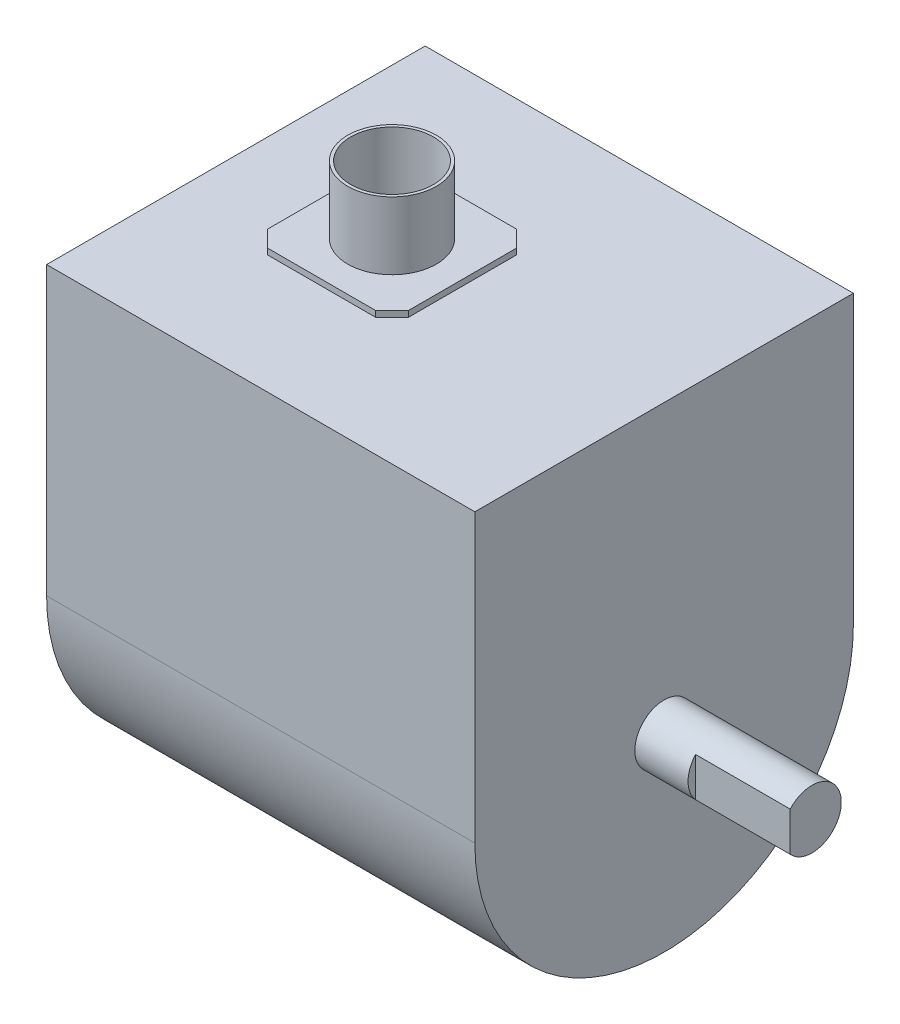
SolidWorks part; units mm, degrees
ref_plane "Front Plane" through (0, 0, 0) normal (0, 0, 1) x (1, 0, 0)
ref_plane "Top Plane" through (0, 0, 0) normal (0, 1, 0) x (1, 0, 0)
ref_plane "Right Plane" through (0, 0, 0) normal (1, 0, 0) x (0, 0, -1)
sketch "Sketch2" plane through (0, 0, 0) normal (1, 0, 0) x (0, 0, -1)
  line L1 (32, 24.25) -> (-32, 24.25)
  line L2 (32, 24.25) -> (32, -24.25)
  line L3 (32, -24.25) -> (-32, -24.25)
  line L4 (-32, 24.25) -> (-32, -24.25)
  line L5 (32, 24.25) -> (-32, -24.25) construction
  line L6 (32, -24.25) -> (-32, 24.25) construction
  arc A0 (32, -24.25) -> (-32, -24.25) centre (0, -24.25) cw
  circle A1 centre (0, -24.25) radius 4.953
  point P0 (0, 0)
  dimension "D3" = 9.906
  dimension "D1" = 48.5
  dimension "D2" = 64
extrude "Boss-Extrude1" add sketch "Sketch2" against normal blind 72.4 contours A1 L3 L2 L1 L4 | A1 L3 A0 | L3 A1 | L3 A1 region at (0, 0.2784, 0) region at (0, -38.113, 0) region at (0, -26.3521, 0) region at (0, -22.1479, 0)
sketch "Sketch3" plane through (0, 24.25, 0) normal (0, 1, 0) x (1, 0, 0)
  line L0 (-72.4, 0) -> (-46, 0) construction
  line L1 (-72.4, 32) -> (-72.4, -32) construction
  line L2 (-55.1313, -9.1313) -> (-55.1313, -11.9126) construction
  line L3 (-55.1313, -9.1313) -> (-57.9126, -9.1313) construction
  line L4 (-55.1313, 9.1313) -> (-36.8687, 9.1313) construction
  line L5 (-55.1313, 9.1313) -> (-55.1313, -9.1313) construction
  line L6 (-55.1313, -9.1313) -> (-36.8687, -9.1313) construction
  line L7 (-36.8687, 9.1313) -> (-36.8687, -9.1313) construction
  line L8 (-55.1313, 9.1313) -> (-36.8687, -9.1313) construction
  line L9 (-55.1313, -9.1313) -> (-36.8687, 9.1313) construction
  line L10 (-57.9126, 11.9126) -> (-34.0874, 11.9126) construction
  line L11 (-57.9126, 11.9126) -> (-57.9126, -11.9126) construction
  line L12 (-57.9126, -11.9126) -> (-34.0874, -11.9126) construction
  line L13 (-34.0874, 11.9126) -> (-34.0874, -11.9126) construction
  line L14 (-57.9126, 11.9126) -> (-34.0874, -11.9126) construction
  line L15 (-57.9126, -11.9126) -> (-34.0874, 11.9126) construction
  line L16 (-55.1313, 9.1313) -> (-57.9126, 9.1313) construction
  line L17 (-55.1313, 9.1313) -> (-55.1313, 11.9126) construction
  line L18 (-36.8687, -9.1313) -> (-36.8687, -11.9126) construction
  line L19 (-36.8687, -9.1313) -> (-34.0874, -9.1313) construction
  line L20 (-36.8687, 9.1313) -> (-34.0874, 9.1313) construction
  line L21 (-36.8687, 9.1313) -> (-36.8687, 11.9126) construction
  line L22 (-57.9126, -9.1313) -> (-55.1313, -11.9126)
  line L23 (-55.1313, -11.9126) -> (-36.8687, -11.9126)
  line L24 (-36.8687, -11.9126) -> (-34.0874, -9.1313)
  line L25 (-34.0874, -9.1313) -> (-34.0874, 9.1313)
  line L26 (-34.0874, 9.1313) -> (-36.8687, 11.9126)
  line L27 (-36.8687, 11.9126) -> (-55.1313, 11.9126)
  line L28 (-55.1313, 11.9126) -> (-57.9126, 9.1313)
  line L29 (-57.9126, 9.1313) -> (-57.9126, -9.1313)
  line L30 (-55.1313, -9.1313) -> (-36.8687, -9.1313) construction
  line L31 (-55.1313, -9.1313) -> (-55.1313, 9.1313) construction
  circle A0 centre (-46, 0) radius 7.493
  circle A1 centre (-55.1313, -9.1313) radius 1.524 construction
  circle A2 centre (-36.8687, -9.1313) radius 1.524 construction
  circle A3 centre (-36.8687, 9.1313) radius 1.524 construction
  circle A4 centre (-55.1313, 9.1313) radius 1.524 construction
  dimension "D4" = 14.986
  dimension "D5" = 3.048
  dimension "D1" = 26.4
  dimension "D2" = 18.2626
  dimension "D3" = 23.8252
  dimension "D8" = 18.2626
  dimension "D9" = 18.2626
  dimension "D6" = 2
  dimension "D7" = 2
extrude "Boss-Extrude3" add sketch "Sketch3" along normal blind 1 contours L29 L22 L23 L24 L25 L26 L27 L28
extrude "Boss-Extrude4" add sketch "Sketch3<4>" along normal blind 12.4 contours A0
sketch "Sketch3<4>" plane through (0, 24.25, 0) normal (0, 1, 0) x (1, 0, 0) same geometry as "Sketch3"
sketch "Sketch6" plane through (0, 36.65, 0) normal (0, 1, 0) x (1, 0, 0)
  circle A0 centre (-46, 0) radius 6.993
  circle A1 centre (-46, 0) radius 7.493 construction
  dimension "D1" = 0.5
extrude "Cut-Extrude1" cut sketch "Sketch6" against normal blind 12.4 contours A0
extrude "Boss-Extrude5" add sketch "Sketch2<3>" along normal blind 25 contours L3 A1 | L3 A1 region at (0, -26.3521, 0) region at (0, -22.1479, 0)
sketch "Sketch2<3>" plane through (0, 0, 0) normal (1, 0, 0) x (0, 0, -1) same geometry as "Sketch2"
sketch "Sketch7" plane through (-72.4, 0, 0) normal (-1, 0, 0) x (0, 0, 1)
  circle A1 centre (0, -24.25) radius 4.953
  circle A2 centre (0, -24.25) radius 4.953 construction
extrude "Boss-Extrude6" add sketch "Sketch7" along normal blind 25 contours A1
ref_plane "Plane1" through (0, -24.25, 0) normal (0, 1, 0) x (1, 0, 0)
sketch "Sketch8" plane through (0, -24.25, 0) normal (0, 1, 0) x (1, 0, 0)
  line L18 (25, -4.953) -> (9, -4.953)
  line L19 (-97.4, -3.683) -> (-97.4, -4.953)
  line L20 (-97.4, 4.953) -> (-97.4, -4.953) construction
  line L21 (-97.4, -3.683) -> (-81.4, -3.683)
  line L22 (-81.4, -3.683) -> (-81.4, -4.953)
  line L23 (-81.4, -4.953) -> (-97.4, -4.953)
  line L24 (0, -4.953) -> (25, -4.953) construction
  line L25 (9, -4.953) -> (9, -3.683)
  line L26 (9, -3.683) -> (25, -3.683)
  line L27 (25, -4.953) -> (25, 4.953) construction
  line L28 (25, -3.683) -> (25, -4.953)
  dimension "D1" = 1.27
  dimension "D2" = 16
extrude "Cut-Extrude2" cut sketch "Sketch8" against normal through all both and the other way through all
